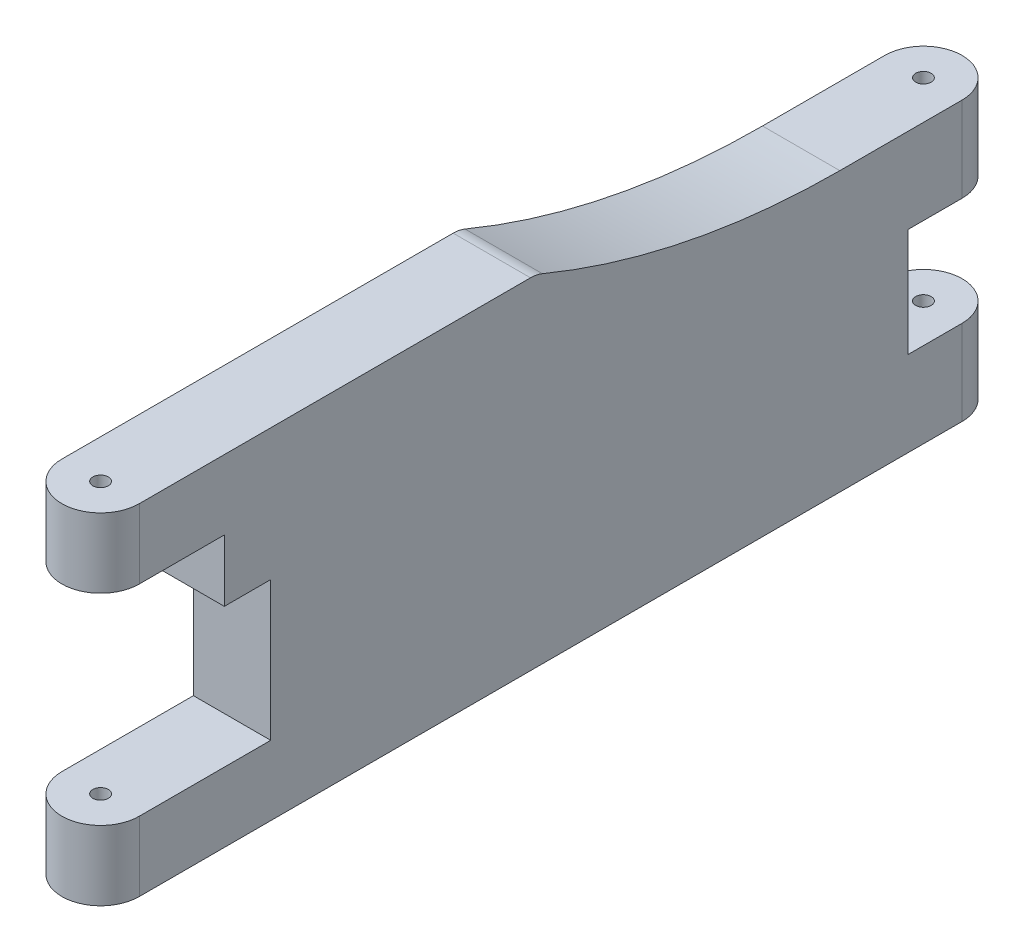
SolidWorks part; units mm, degrees
ref_plane "Front Plane" through (0, 0, 0) normal (0, 0, 1) x (1, 0, 0)
ref_plane "Top Plane" through (0, 0, 0) normal (0, 1, 0) x (1, 0, 0)
ref_plane "Right Plane" through (0, 0, 0) normal (1, 0, 0) x (0, 0, -1)
sketch "SketchSide" plane through (0, 0, 0) normal (0, 1, 0) x (1, 0, 0)
  line L0 (-2.5, -24.7781) -> (-2.5, 0)
  line L1 (2.5, -53.2) -> (2.5, 0)
  line L2 (-2.5, -53.2) -> (-2.5, -24.7781)
  arc A0 (2.5, 0) -> (-2.5, 0) centre (0, 0) ccw
  circle A1 centre (0, 0) radius 0.5
  arc A2 (2.5, -53.2) -> (-2.5, -53.2) centre (0, -53.2) cw
  circle A3 centre (0, -53.2) radius 0.5
  dimension "D1" = 5
  dimension "D2" = 2.5
  dimension "D4" = 1
  dimension "D5" = 2.5
  dimension "D3" = 53.2
extrude "BossExtrudeSide" add sketch "SketchSide" along normal blind 22
sketch "SketchDistalRoom" plane through (0, 0, 0) normal (1, 0, 0) x (0, 0, -1)
  line L0 (0, 0) -> (-53.2, 0) construction
  line L1 (-55.7, 22) -> (-55.7, 0) construction
  line L2 (-44.7, 13.5) -> (-47.7, 13.5)
  line L3 (-47.7, 13.5) -> (-47.7, 17.5)
  line L5 (-55.7, 17.5) -> (-47.7, 17.5)
  line L6 (-44.7, 13.5) -> (-44.7, 4.5)
  line L7 (-44.7, 4.5) -> (-55.7, 4.5)
  line L8 (-55.7, 4.5) -> (-55.7, 17.5)
  dimension "D1" = 13
  dimension "D2" = 4.5
  dimension "D3" = 3
  dimension "D4" = 11
  dimension "D5" = 4
extrude "CutExtrudeDistalRoom" cut sketch "SketchDistalRoom" against normal through all both and the other way through all
sketch "SketchSesorRoom" plane through (0, 0, 0) normal (1, 0, 0) x (0, 0, -1)
  line L0 (-36.7, 14) -> (-36.7, 4)
  line L2 (-36.7, 4) -> (-31.7, 4)
  line L3 (-31.7, 4) -> (-31.7, 14)
  line L4 (-31.7, 14) -> (-36.7, 14)
  line L5 (0, 22) -> (-53.2, 22) construction
  line L6 (0, 0) -> (-53.2, 0) construction
  line L7 (-44.7, 4.5) -> (-44.7, 13.5) construction
  dimension "D1" = 8
  dimension "D2" = 4
  dimension "D3" = 5
  dimension "D4" = 8
extrude "CutExtrudeSensorRoom" cut sketch "SketchSesorRoom" against normal blind 10
sketch "SketchStrongSide" plane through (0, 0, 0) normal (1, 0, 0) x (0, 0, -1)
  line L0 (2.5, 18) -> (-27.5, 18)
  line L1 (2.5, 0) -> (2.5, 22) construction
  line L2 (-27.5, 18) -> (-27.5, 22)
  line L3 (-27.5, 22) -> (2.5, 22)
  line L4 (2.5, 22) -> (2.5, 18)
  line L5 (-53.2, 0) -> (0, 0) construction
  line L6 (-53.2, 22) -> (0, 22) construction
  dimension "D1" = 18
  dimension "D2" = 30
extrude "CutExtrudeStrongSide" cut sketch "SketchStrongSide" against normal through all both and the other way through all
fillet "FilletStrongSide" radius 50 1 edges at (0, 18, 27.5)
fillet "FilletSide" radius 2 1 edges at (0, 22, 27.5)
sketch "SketchSpringRoom" plane through (0, 0, 0) normal (1, 0, 0) x (0, 0, -1)
  line L0 (2.5, 5.5) -> (-3.5, 5.5)
  line L1 (2.5, 0) -> (2.5, 18) construction
  line L2 (-3.5, 5.5) -> (-3.5, 12.5)
  line L3 (-3.5, 12.5) -> (2.5, 12.5)
  line L4 (2.5, 12.5) -> (2.5, 5.5)
  line L5 (-53.2, 0) -> (0, 0) construction
  dimension "D1" = 6
  dimension "D2" = 7
  dimension "D3" = 5.5
extrude "CutExtrudeSpringRoom" cut sketch "SketchSpringRoom" against normal through all both and the other way through all
